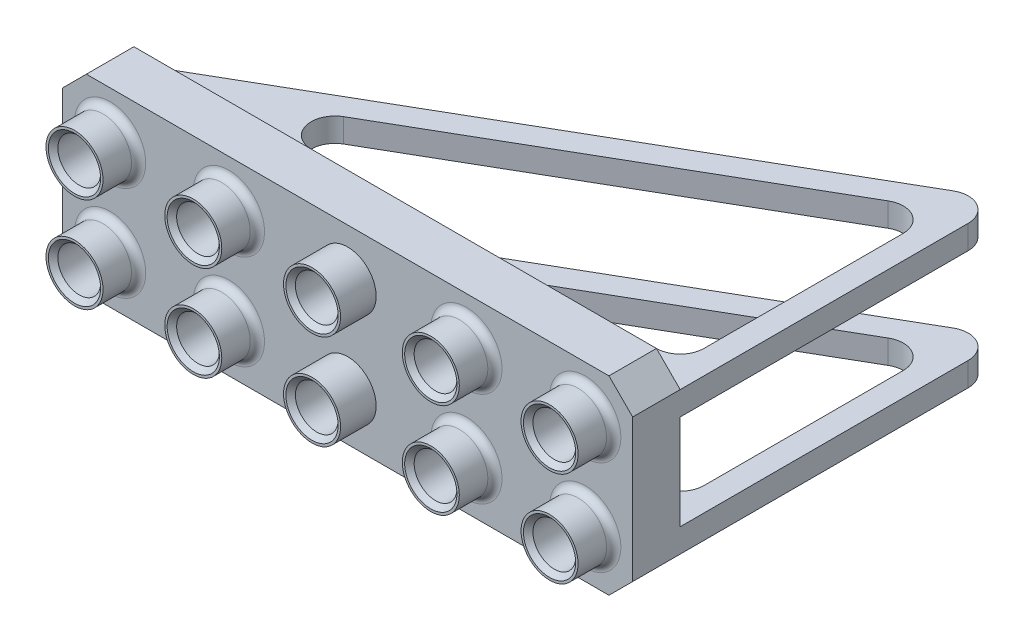
SolidWorks part; units mm, degrees
material "6061 合金"
ref_plane "前视基准面" through (0, 0, 0) normal (0, 0, 1) x (1, 0, 0)
ref_plane "上视基准面" through (0, 0, 0) normal (0, 1, 0) x (1, 0, 0)
ref_plane "右视基准面" through (0, 0, 0) normal (1, 0, 0) x (0, 0, -1)
sketch "草图1" plane through (0, 0, 0) normal (0, 0, 1) x (1, 0, 0)
  line L0 (-100, 40) -> (-100, 20) construction
  line L1 (-120, -40) -> (120, -40)
  line L2 (-120, -40) -> (-120, 40)
  line L3 (-120, 40) -> (120, 40)
  line L4 (120, -40) -> (120, 40)
  line L5 (-120, -40) -> (120, 40) construction
  line L6 (-120, 40) -> (120, -40) construction
  line L7 (-100, 20) -> (-120, 20) construction
  line L8 (-100, -20) -> (-100, 20) construction
  line L9 (-100, 20) -> (-50, 20) construction
  line L10 (-100, 0) -> (0, 0) construction
  line L11 (0, 20) -> (0, 0) construction
  circle A0 centre (-100, 20) radius 9 construction
  circle A1 centre (-50, 20) radius 9 construction
  circle A2 centre (0, 20) radius 9 construction
  circle A3 centre (50, 20) radius 9 construction
  circle A4 centre (100, 20) radius 9 construction
  circle A5 centre (-50, -20) radius 9 construction
  circle A6 centre (0, -20) radius 9 construction
  circle A7 centre (50, -20) radius 9 construction
  circle A8 centre (100, -20) radius 9 construction
  circle A17 centre (-100, -20) radius 9 construction
  point P0 (0, 0)
  dimension "D3" = 18
  dimension "D7" = 40
  dimension "D8" = 50
  dimension "D1" = 80
  dimension "D2" = 240
  dimension "D4" = 20
  dimension "D5" = 5
  dimension "D6" = 2
extrude "凸台-拉伸1" add sketch "草图1" along normal blind 20
sketch "草图2" plane through (0, 0, 20) normal (0, 0, 1) x (1, 0, 0)
  circle A0 centre (-100, 20) radius 9 construction
  circle A1 centre (-100, 20) radius 9
  circle A2 centre (-50, 20) radius 9
  circle A3 centre (0, 20) radius 9
  circle A4 centre (50, 20) radius 9
  circle A5 centre (100, 20) radius 9
  circle A6 centre (-50, -20) radius 9
  circle A7 centre (0, -20) radius 9
  circle A8 centre (50, -20) radius 9
  circle A9 centre (100, -20) radius 9
  circle A18 centre (-100, -20) radius 9
  circle A21 centre (-100, 20) radius 12
  circle A22 centre (-50, 20) radius 12
  circle A23 centre (0, 20) radius 12
  circle A24 centre (50, 20) radius 12
  circle A25 centre (100, 20) radius 12
  circle A26 centre (-50, -20) radius 12
  circle A27 centre (0, -20) radius 12
  circle A28 centre (50, -20) radius 12
  circle A29 centre (100, -20) radius 12
  circle A38 centre (-100, -20) radius 12
  dimension "D3" = 50
  dimension "D4" = 24
  dimension "D1" = 5
  dimension "D2" = 2
extrude "凸台-拉伸2" add sketch "草图2" along normal blind 15
sketch "草图3" plane through (0, 0, 20) normal (0, 0, 1) x (1, 0, 0)
  line L0 (-100, 20) -> (-50, 20) construction
  line L1 (-100, 20) -> (-100, -20) construction
  circle A0 centre (-100, 20) radius 9
  circle A1 centre (-50, 20) radius 9
  circle A2 centre (0, 20) radius 9
  circle A3 centre (50, 20) radius 9
  circle A4 centre (100, 20) radius 9
  circle A5 centre (-50, -20) radius 9
  circle A6 centre (0, -20) radius 9
  circle A7 centre (50, -20) radius 9
  circle A8 centre (100, -20) radius 9
  circle A17 centre (-100, -20) radius 9
  circle A20 centre (-100, 20) radius 9 construction
  circle A21 centre (-50, 20) radius 9 construction
  circle A22 centre (-100, -20) radius 9 construction
  dimension "D2" = 5
  dimension "D3" = 2
extrude "切除-拉伸1" cut sketch "草图3" against normal blind 15
chamfer "倒角1" distance 10 angle 45 4 edges at (120, 40, 10) (120, -40, 10) (-120, -40, 10) (-120, 40, 10)
fillet "圆角1" radius 3 18 edges at (-112, 20, 20) (-91, -20, 5) (109, -20, 5) (59, -20, 5) (9, -20, 5) (-41, -20, 5) (109, 20, 5) (59, 20, 5) (9, 20, 5) (-41, 20, 5) (-91, 20, 5) (-62, 20, 20) (38, 20, 20) (88, 20, 20) (-62, -20, 20) (38, -20, 20) (88, -20, 20) (-112, -20, 20)
chamfer "倒角2" distance 2 angle 45 10 edges at (109, -20, 35) (59, -20, 35) (9, -20, 35) (-41, -20, 35) (-91, -20, 35) (109, 20, 35) (59, 20, 35) (9, 20, 35) (-41, 20, 35) (-91, 20, 35)
sketch "草图4" plane through (0, 0, 0) normal (1, 0, 0) x (0, 0, -1)
  line L0 (0, 40) -> (3.812, 40)
  line L1 (3.812, 40) -> (50, -40)
  line L2 (50, -40) -> (0, -40)
  line L3 (10, 9.282) -> (32.6795, -30)
  line L4 (32.6795, -30) -> (10, -30)
  line L5 (10, -30) -> (10, 9.282)
  line L6 (0, -30) -> (0, 30) construction
  line L7 (0, 40) -> (0, -40)
  dimension "D1" = 60
  dimension "D2" = 10
  dimension "D3" = 10
  dimension "D4" = 10
  dimension "D5" = 50
extrude "凸台-拉伸3" [suppressed] add sketch "草图4" along normal blind 10 from offset 50
mirror "镜向1" [suppressed] about plane through (0, 0, 0) normal (1, 0, 0)
fillet "圆角2" [suppressed] radius 5
sketch "草图5" plane through (0, 40, 0) normal (0, 1, 0) x (1, 0, 0)
  line L0 (-120, 0) -> (120, 138.5641)
  line L1 (120, 138.5641) -> (120, 0)
  line L2 (120, 0) -> (-120, 0)
  line L3 (110, 121.2436) -> (110, 10)
  line L4 (110, 10) -> (-82.6795, 10)
  line L5 (-82.6795, 10) -> (110, 121.2436)
  dimension "D1" = 10
  dimension "D2" = 10
  dimension "D3" = 10
  dimension "D4" = 60
extrude "凸台-拉伸4" add sketch "草图5" against normal blind 10 from offset 10 offset against normal yes
mirror "镜向2" about plane through (0, 0, 0) normal (0, 1, 0) of "凸台-拉伸4"
fillet "圆角3" radius 10 8 edges at (120, -25, -138.5641) (120, 25, -138.5641) (-82.6795, -25, -10) (110, -25, -121.2436) (110, -25, -10) (-82.6795, 25, -10) (110, 25, -121.2436) (110, 25, -10)
